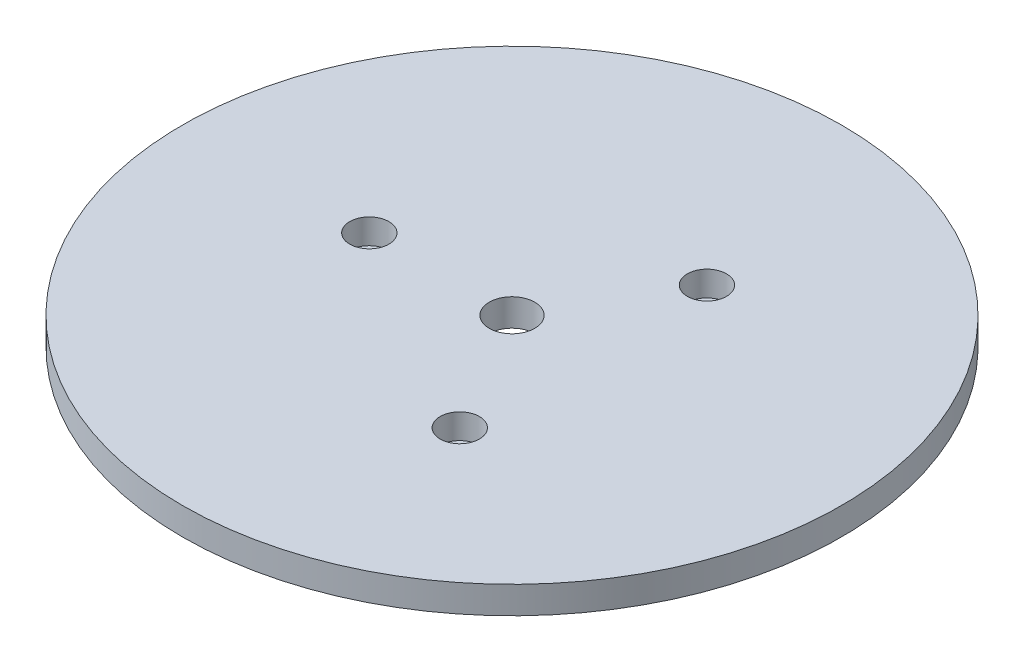
SolidWorks part; units mm, degrees
ref_plane "Front Plane" through (0, 0, 0) normal (0, 0, 1) x (1, 0, 0)
ref_plane "Top Plane" through (0, 0, 0) normal (0, 1, 0) x (1, 0, 0)
ref_plane "Right Plane" through (0, 0, 0) normal (1, 0, 0) x (0, 0, -1)
sketch "Sketch1" plane through (0, 0, 0) normal (0, 1, 0) x (1, 0, 0)
  circle A0 centre (0, 0) radius 72.5
  dimension "FLANGE_OD" = 145
extrude "Boss-Extrude1" add sketch "Sketch1" along normal blind 6
sketch "Sketch2" plane through (0, 0, 0) normal (0, 1, 0) x (1, 0, 0)
  circle A0 centre (0, 0) radius 5
  dimension "BORE_D" = 10
extrude "Cut-Extrude1" cut sketch "Sketch2" along normal through all
sketch "Sketch3" plane through (0, 6, 0) normal (0, 1, 0) x (1, 0, 0)
  circle A0 centre (0, 0) radius 31.3916 construction
  circle A1 centre (-31.3916, 0) radius 4.3083
  dimension "BOLT_D" = 8.6167
  dimension "BOLT_PCD" = 62.7831
extrude "Cut-Extrude2" cut sketch "Sketch3" against normal blind 5.4911
pattern_circular "CirPattern1" count 3 over 360 about axis through (0, 0, 0) along (0, 1, 0) of "Cut-Extrude2"
